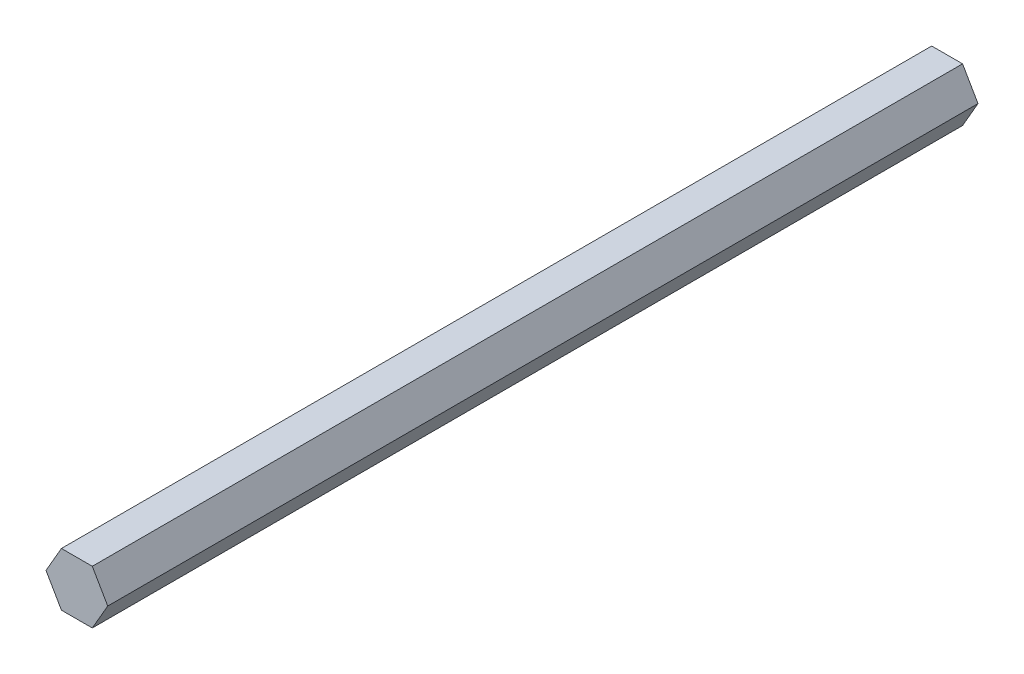
SolidWorks part; units mm, degrees
note: '?' marks a value the reader was unsure of.
ref_plane "Front Plane" through (0, 0, 0) normal (0, 0, 1) x (1, 0, 0)
ref_plane "Top Plane" through (0, 0, 0) normal (0, 1, 0) x (1, 0, 0)
ref_plane "Right Plane" through (0, 0, 0) normal (1, 0, 0) x (0, 0, -1)
sketch "Sketch1" plane through (0, 0, 0) normal (0, 0, 1) x (1, 0, 0)
  line L1 (3.6662, 6.35) -> (-3.6662, 6.35)
  line L2 (-3.6662, 6.35) -> (-7.3323, 0)
  line L3 (-7.3323, 0) -> (-3.6662, -6.35)
  line L4 (-3.6662, -6.35) -> (3.6662, -6.35)
  line L5 (3.6662, -6.35) -> (7.3323, 0)
  line L6 (7.3323, 0) -> (3.6662, 6.35)
  circle A0 centre (0, 0) radius 6.35 construction
  dimension "D1" = 12.7
extrude "Boss-Extrude1" add sketch "Sketch1" along normal mid plane 206.756
ref_axis "Axis1" through (0, 0, -83.82) along (0, 0, 1)?
